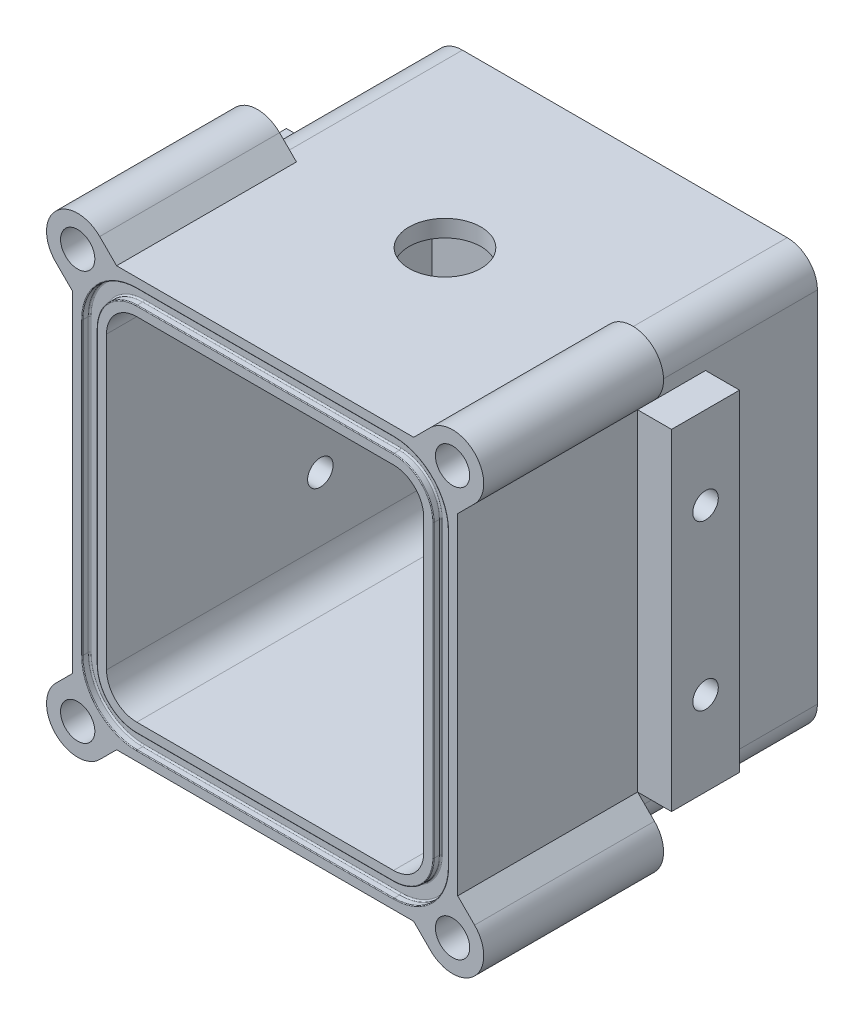
SolidWorks part; units mm, degrees
material "ABS"
ref_plane "X-Y Datum" through (0, 0, 0) normal (0, 0, 1) x (1, 0, 0)
ref_plane "X-Z Datum" through (0, 0, 0) normal (0, 1, 0) x (1, 0, 0)
ref_plane "Y-Z Datum" through (0, 0, 0) normal (1, 0, 0) x (0, 0, -1)
sketch "Sketch1" plane through (0, 0, 0) normal (0, 0, 1) x (1, 0, 0)
  line L0 (-34, -37) -> (-34, -16.68)
  line L1 (34, 37) -> (-34, 37)
  line L2 (34, 37) -> (34, -37)
  line L3 (34, -37) -> (-34, -37)
  line L5 (34, 37) -> (-34, -37) construction
  line L6 (34, -37) -> (-34, 37) construction
  line L7 (55.1739, 0) -> (-55.1739, 0) construction
  line L8 (-34, 37) -> (-34, 16.68)
  line L9 (-34, 16.68) -> (-34, -16.68)
  arc A0 (-34, -16.68) -> (-34, 16.68) centre (-14.8444, 0) cw construction
  point P0 (0, 0)
  dimension "D2" = 25.4
  dimension "D1" = 74
  dimension "D3" = 20.32
  dimension "D4" = 68
extrude "Boss-Extrude1" add sketch "Sketch1" along normal mid plane 63.5
shell "Shell1" thickness 6 removed face at (0, 0, 31.75)
fillet "Fillet1" radius 5.334 8 edges at (34, 37, 0) (34, -37, 0) (-34, -37, 0) (-34, 37, 0) (28, 31, 3) (28, -31, 3) (-28, -31, 3) (-28, 31, 3)
sketch "Sketch2" plane through (0, 0, 31.75) normal (0, 0, 1) x (1, 0, 0)
  line L21 (32.2827, -25.666) -> (32.2827, 25.666)
  line L22 (22.666, 35.2827) -> (-22.666, 35.2827)
  line L23 (-32.2827, 25.666) -> (-32.2827, -25.666)
  line L24 (-22.666, -35.2827) -> (22.666, -35.2827)
  line L25 (31, -25.666) -> (31, 25.666)
  line L26 (-22.666, -34) -> (22.666, -34)
  line L27 (-31, 25.666) -> (-31, -25.666)
  line L28 (22.666, 34) -> (-22.666, 34)
  line L29 (31, -25.666) -> (31, 25.666) construction
  line L30 (-22.666, -34) -> (22.666, -34) construction
  line L31 (-31, 25.666) -> (-31, -25.666) construction
  line L32 (22.666, 34) -> (-22.666, 34) construction
  line L33 (-29.7173, 25.666) -> (-29.7173, -25.666)
  line L34 (-22.666, -32.7173) -> (22.666, -32.7173)
  line L35 (29.7173, -25.666) -> (29.7173, 25.666)
  line L36 (22.666, 32.7173) -> (-22.666, 32.7173)
  arc A15 (32.2827, 25.666) -> (22.666, 35.2827) centre (22.666, 25.666) ccw
  arc A16 (-22.666, 35.2827) -> (-32.2827, 25.666) centre (-22.666, 25.666) ccw
  arc A17 (-32.2827, -25.666) -> (-22.666, -35.2827) centre (-22.666, -25.666) ccw
  arc A18 (22.666, -35.2827) -> (32.2827, -25.666) centre (22.666, -25.666) ccw
  arc A19 (31, 25.666) -> (22.666, 34) centre (22.666, 25.666) ccw
  arc A20 (22.666, -34) -> (31, -25.666) centre (22.666, -25.666) ccw
  arc A21 (-31, -25.666) -> (-22.666, -34) centre (-22.666, -25.666) ccw
  arc A22 (-22.666, 34) -> (-31, 25.666) centre (-22.666, 25.666) ccw
  arc A23 (31, 25.666) -> (22.666, 34) centre (22.666, 25.666) ccw construction
  arc A24 (22.666, -34) -> (31, -25.666) centre (22.666, -25.666) ccw construction
  arc A25 (-31, -25.666) -> (-22.666, -34) centre (-22.666, -25.666) ccw construction
  arc A26 (-22.666, 34) -> (-31, 25.666) centre (-22.666, 25.666) ccw construction
  arc A27 (-22.666, 32.7173) -> (-29.7173, 25.666) centre (-22.666, 25.666) ccw
  arc A28 (-29.7173, -25.666) -> (-22.666, -32.7173) centre (-22.666, -25.666) ccw
  arc A29 (22.666, -32.7173) -> (29.7173, -25.666) centre (22.666, -25.666) ccw
  arc A30 (29.7173, 25.666) -> (22.666, 32.7173) centre (22.666, 25.666) ccw
  dimension "D4" = 7.0513
  dimension "D5" = 2.5654
  dimension "D1" = 3
  dimension "D2" = 1.2827
  dimension "D3" = 1.2827
extrude "Cut-Extrude1" cut sketch "Sketch2" against normal blind 1.2954
fillet "Fillet2" radius 0.254 16 edges at (27.652, -30.652, 30.4546) (0, -32.7173, 30.4546) (-27.652, -30.652, 30.4546) (-29.7173, 0, 30.4546) (-27.652, 30.652, 30.4546) (0, 32.7173, 30.4546) (27.652, 30.652, 30.4546) (-29.466, 32.466, 30.4546) (0, 35.2827, 30.4546) (29.466, 32.466, 30.4546) (32.2827, 0, 30.4546) (29.466, -32.466, 30.4546) (0, -35.2827, 30.4546) (-29.466, -32.466, 30.4546) (29.7173, 0, 30.4546) (-32.2827, 0, 30.4546)
fillet "Fillet3" radius 0.127 16 edges at (-29.466, -32.466, 31.75) (-32.2827, 0, 31.75) (-29.466, 32.466, 31.75) (0, 35.2827, 31.75) (29.466, 32.466, 31.75) (32.2827, 0, 31.75) (29.466, -32.466, 31.75) (-27.652, -30.652, 31.75) (-29.7173, 0, 31.75) (-27.652, 30.652, 31.75) (0, 32.7173, 31.75) (27.652, 30.652, 31.75) (29.7173, 0, 31.75) (27.652, -30.652, 31.75) (0, -35.2827, 31.75) (0, -32.7173, 31.75)
sketch "Sketch3" plane through (0, 0, 31.75) normal (0, 0, 1) x (1, 0, 0)
  line L0 (22.666, -25.666) -> (37.7124, -40.7124) construction
  line L1 (29.2023, -39.9805) -> (26.2218, -37)
  line L2 (-28.666, -37) -> (28.666, -37) construction
  line L3 (22.666, -25.666) -> (0, 0)
  line L5 (34, -29.2218) -> (36.9805, -32.2023)
  line L6 (34, -31.666) -> (34, 31.666) construction
  arc A0 (22.666, -35.4097) -> (32.4097, -25.666) centre (22.666, -25.666) ccw construction
  arc A1 (22.666, -35.4097) -> (32.4097, -25.666) centre (22.666, -25.666) ccw
  circle A2 centre (33.0914, -36.0914) radius 3.025
  circle A3 centre (33.0914, -36.0914) radius 5.5
  point P7 (29.5558, -32.5558)
  arc M9 (32.4097, -25.666) -> (22.666, -35.4097) centre (22.666, -25.666) cw
  line M14 (-28.666, -37) -> (28.666, -37)
  arc M15 (28.666, -37) -> (34, -31.666) centre (28.666, -31.666) ccw
  line M16 (34, -31.666) -> (34, 31.666)
  dimension "D1" = 6.05
  dimension "D3" = 11
  dimension "D2" = 5
extrude "Boss-Extrude2" add sketch "Sketch3" against normal blind 31.75 contours L0 A2 A3 M15 M14 | A2 L0 A3 M16 M15 | L0 A2 M15 | L0 A2 M15 | A2 L0 M15 | A3 M14 | A3 M16 | A1 L0 A2 A3 M15 M16 | L0 A2 M15 | L0 A3 A2 M9 M14 M15 region at (32.0118, -32.0896, 31.75) region at (29.0896, -35.0118, 31.75) region at (32.4421, -34.0333, 31.75) region at (31.0333, -35.4421, 31.75) region at (34.789, -30.4552, 31.75) region at (36.5269, -35.0577, 31.75) region at (32.0577, -39.5269, 31.75) region at (27.4552, -37.789, 31.75) region at (34.5525, -35.5923, 31.75) region at (32.5923, -37.5525, 31.75)
sketch "Sketch4" plane through (0, 0, 31.75) normal (0, 0, 1) x (1, 0, 0)
  circle A0 centre (33.0914, -36.0914) radius 3.025 construction
  circle A1 centre (33.0914, -36.0914) radius 3.025
  dimension "D1" = 6.05
extrude "Cut-Extrude2" cut sketch "Sketch4" against normal blind 9
mirror "Mirror1" about plane through (0, 0, 0) normal (0, 1, 0) of "Cut-Extrude2", "Boss-Extrude2"
mirror "Mirror2" about plane through (0, 0, 0) normal (1, 0, 0) of "Mirror1", "Cut-Extrude2", "Boss-Extrude2"
sketch "Sketch6" plane through (0, 37, 0) normal (0, 1, 0) x (1, 0, 0)
  line L0 (28.666, 31.75) -> (-28.666, 31.75) construction
  line L1 (0, -31.75) -> (0, 31.75) construction
  line L2 (26.2218, -31.75) -> (-26.2218, -31.75) construction
  circle A0 centre (0, 0) radius 6.35
  circle A1 centre (0, 0) radius 11.43
  point P9 (0, 0)
  dimension "D1" = 12.7
  dimension "D2" = 22.86
extrude "Cut-Extrude3" cut sketch "Sketch6" against normal blind 6 contours A0 L1 | L1 A0 region at (-2.695, 37, 0) region at (2.695, 37, 0)
sketch "Sketch7" plane through (0, 31, 0) normal (0, -1, 0) x (1, 0, 0)
  circle A1 centre (0, 0) radius 11.43
  circle A2 centre (0, 0) radius 11.43
  circle A3 centre (0, 0) radius 6.35
  circle A4 centre (0, 0) radius 6.35
  dimension "D1" = 0
  dimension "D2" = 0
extrude "Cut-Extrude4" cut sketch "Sketch7" against normal blind 3
sketch "Sketch8" plane through (-34, 0, 0) normal (-1, 0, 0) x (0, 0, 1)
  line L5 (0, 0) -> (0, 29.2218)
  line L6 (0, 0) -> (0, -29.2218)
  line L7 (0, -29.2218) -> (-12, -29.2218)
  line L8 (0, 29.2218) -> (-12, 29.2218)
  line L9 (-12, 29.2218) -> (-12, -29.2218)
  point P0 (0, 0)
extrude "Boss-Extrude3" add sketch "Sketch8" along normal blind 6
sketch "Sketch9" plane through (-40, 0, 0) normal (-1, 0, 0) x (0, 0, 1)
  line L0 (-6, 29.2218) -> (-6, -29.2218)
  line L3 (-12, 0) -> (0, 0) construction
  line L4 (-12, 29.2218) -> (-12, -29.2218) construction
  line L5 (0, 29.2218) -> (-12, 29.2218) construction
  line L6 (-12, -29.2218) -> (0, -29.2218) construction
  circle A0 centre (-6, 14.6109) radius 2
  circle A1 centre (-6, -14.3531) radius 2
  dimension "D2" = 4
  dimension "D3" = 4
  dimension "D1" = 14.6109
  dimension "D4" = 28.964
extrude "Cut-Extrude5" cut sketch "Sketch9" against normal blind 4 contours L0 A1 | L0 A1 | L0 A0 | L0 A0 region at (-40, 14.6109, -5.1512) region at (-40, -14.3531, -5.1512) region at (-40, -14.3531, -6.8488) region at (-40, 14.6109, -6.8488)
mirror "Mirror5" about plane through (0, 0, 0) normal (1, 0, 0) of "Boss-Extrude3"
mirror "Mirror6" about plane through (0, 0, 0) normal (1, 0, 0) of "Cut-Extrude5"
hole_wizard "M4 Clearance Hole1" positions "Sketch10" profile "Sketch11" hole size "M4" standard "ANSI Metric" end condition through all
sketch "Sketch10" plane through (-36, 0, 0) normal (-1, 0, 0) x (0, 0, 1)
  point P0 (-6, 14.6109)
  point P3 (-6, -14.3531)
sketch "Sketch11" plane through (-36, 14.6109, -6) normal (0, 1, 0) x (0, 0, 1)
  line L0 (0, 0) -> (0, 76)
  line L1 (0, 76) -> (2.25, 76)
  line L2 (2.25, 76) -> (2.25, 0)
  line L5 (2.25, 0) -> (0, 0)
  line L11 (0, -6.35) -> (0, 107.95) construction
  dimension "Thru Hole Dia." = 4.5
  dimension "Thru Hole Depth" = 76
